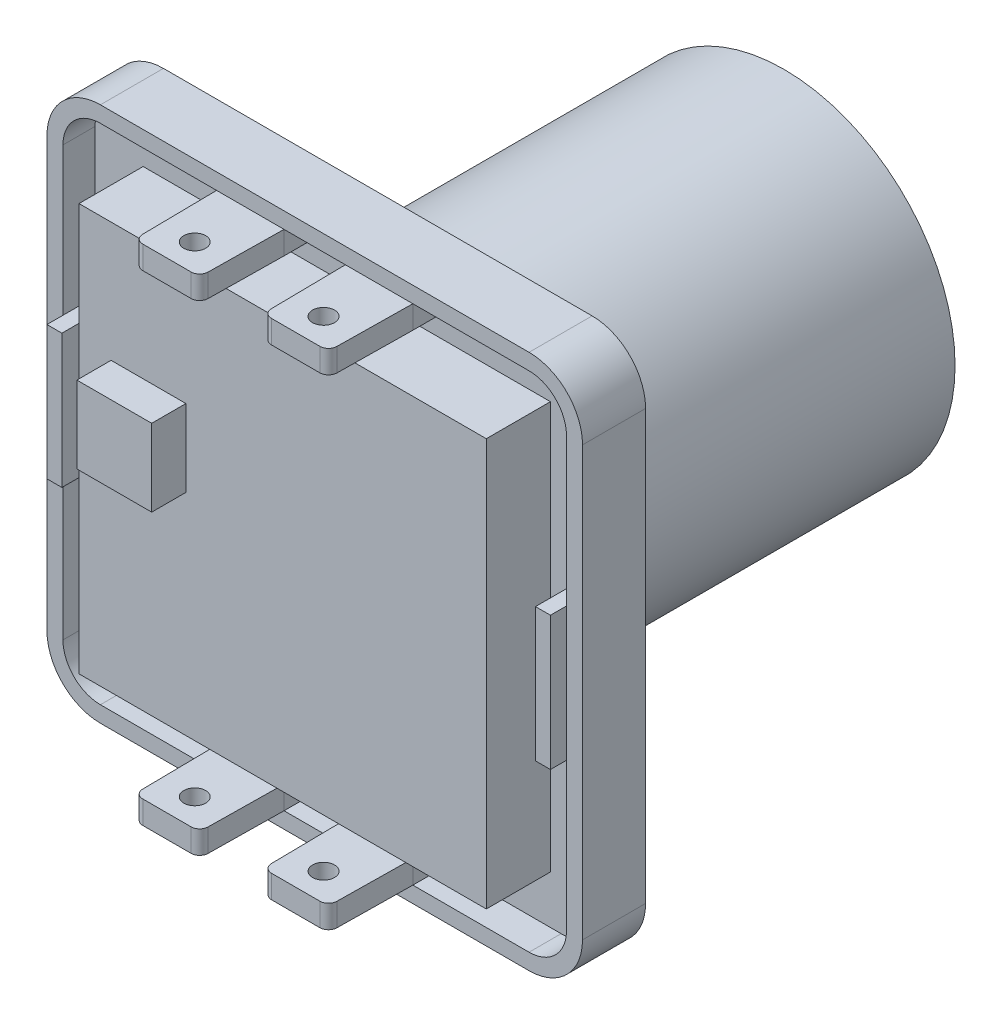
SolidWorks part; units mm, degrees
ref_plane "前视基准面" through (0, 0, 0) normal (0, 0, 1) x (1, 0, 0)
ref_plane "上视基准面" through (0, 0, 0) normal (0, 1, 0) x (1, 0, 0)
ref_plane "右视基准面" through (0, 0, 0) normal (1, 0, 0) x (0, 0, -1)
sketch "草图1" plane through (0, 0, 0) normal (0, 0, 1) x (1, 0, 0)
  line L1 (-25.05, 25.05) -> (25.05, 25.05)
  line L2 (-25.05, 25.05) -> (-25.05, -25.05)
  line L3 (-25.05, -25.05) -> (25.05, -25.05)
  line L4 (25.05, 25.05) -> (25.05, -25.05)
  line L5 (-25.05, 25.05) -> (25.05, -25.05) construction
  line L6 (-25.05, -25.05) -> (25.05, 25.05) construction
  point P0 (0, 0)
  dimension "D1" = 50.1
  dimension "D2" = 50.1
extrude "凸台-拉伸1" add sketch "草图1" against normal blind 5.9
sketch "草图2" plane through (0, 0, 0) normal (0, 0, 1) x (1, 0, 0)
  line L0 (25.05, -25.05) -> (25.05, 25.05) construction
  line L1 (22.15, 6.25) -> (23.55, 6.25)
  line L2 (22.15, 6.25) -> (22.15, -6.25)
  line L3 (22.15, -6.25) -> (23.55, -6.25)
  line L4 (23.55, 6.25) -> (23.55, -6.25)
  line L5 (22.15, 6.25) -> (23.55, -6.25) construction
  line L6 (22.15, -6.25) -> (23.55, 6.25) construction
  point P0 (22.85, 0)
  dimension "D1" = 12.5
  dimension "D2" = 1.5
  dimension "D3" = 1.4
extrude "凸台-拉伸2" add sketch "草图2" along normal blind 1.5
mirror "镜向1" about plane through (0, 0, 0) normal (1, 0, 0) of "凸台-拉伸2"
sketch "草图3" plane through (0, 0, 0) normal (0, 0, 1) x (1, 0, 0)
  line L0 (-2.87, 23.55) -> (-2.87, 21.4)
  line L1 (-9.18, 23.55) -> (9.18, 23.55)
  line L2 (-9.18, 23.55) -> (-9.18, 21.4)
  line L3 (-9.18, 21.4) -> (9.18, 21.4)
  line L4 (9.18, 23.55) -> (9.18, 21.4)
  line L5 (-9.18, 23.55) -> (9.18, 21.4) construction
  line L6 (-9.18, 21.4) -> (9.18, 23.55) construction
  line L7 (2.87, 23.55) -> (2.87, 21.4)
  line L8 (25.05, 25.05) -> (-25.05, 25.05) construction
  point P0 (0, 22.475)
  dimension "D1" = 1.5
  dimension "D2" = 18.36
  dimension "D3" = 2.15
  dimension "D4" = 5.74
  dimension "D5" = 2.87
extrude "凸台-拉伸3" add sketch "草图3" along normal blind 7.8 contours L2 L3 L0 L1 | L1 L7 L3 L4 region at (-6.025, 22.475, 0) region at (6.025, 22.475, 0)
sketch "草图5" plane through (0, 23.55, 0) normal (0, 1, 0) x (1, 0, 0)
  line L0 (-9.18, 0) -> (-9.075, -7.8)
  line L1 (-9.18, -7.8) -> (-2.87, -7.8) construction
  line L2 (-9.075, -7.8) -> (-9.18, -7.8)
  line L3 (-9.18, -7.8) -> (-9.18, 0)
  line L4 (-6.025, 0) -> (-6.025, -7.8) construction
  line L5 (-9.18, 0) -> (-2.87, 0) construction
  line L6 (-2.87, -7.8) -> (-2.87, 0)
  line L7 (-2.975, -7.8) -> (-2.87, -7.8)
  line L8 (-2.87, 0) -> (-2.975, -7.8)
  dimension "D1" = 6.1
extrude "切除-拉伸1" cut sketch "草图5" against normal blind 7.8
mirror "镜向2" about plane through (0, 0, 0) normal (1, 0, 0) of "切除-拉伸1"
sketch "草图6" plane through (0, 23.55, 0) normal (0, 1, 0) x (1, 0, 0)
  line L0 (-6.025, 0) -> (-6.025, -7.8) construction
  line L1 (-9.18, 0) -> (-2.87, 0) construction
  line L2 (-9.075, -7.8) -> (-2.975, -7.8) construction
  line L3 (0, 0) -> (0, -3.8203) construction
  circle A0 centre (-6.025, -5.2) radius 1
  circle A1 centre (6.025, -5.2) radius 1
  dimension "D1" = 2.6
  dimension "D2" = 2
extrude "切除-拉伸2" cut sketch "草图6" against normal blind 7.8
hole_wizard "M2.5 螺纹孔1" positions "草图7" profile "草图8" tap size "M2.5" standard "GB" end condition through all
sketch "草图7" plane through (0, 23.55, 0) normal (0, 1, 0) x (1, 0, 0)
  point P0 (-6.025, -5.2)
  point P3 (6.025, -5.2)
sketch "草图8" plane through (-6.025, 23.55, 5.2) normal (1, 0, 0) x (0, 0, 1)
  line L0 (0, 0) -> (0, 48.6)
  line L1 (0, 48.6) -> (1.025, 48.6)
  line L2 (1.025, 48.6) -> (1.025, 0)
  line L5 (1.025, 0) -> (0, 0)
  line L11 (0, -6.35) -> (0, 107.95) construction
  dimension "通孔螺纹孔钻头直径" = 2.05
  dimension "通孔螺纹孔钻头深度" = 48.6
cosmetic thread "孔螺蚊线1" parameters "D2"=2.5
cosmetic thread "孔螺蚊线2" parameters "D2"=2.5
fillet "圆角1" radius 0.8 4 edges at (9.075, 22.475, 7.8) (2.975, 22.475, 7.8) (-2.975, 22.475, 7.8) (-9.075, 22.475, 7.8)
mirror "镜向3" about plane through (0, 0, 0) normal (0, 1, 0) of "凸台-拉伸3", "切除-拉伸1", "镜向2", "M2.5 螺纹孔1", "切除-拉伸2", "圆角1"
sketch "草图9" plane through (0, 0, 0) normal (0, 0, 1) x (1, 0, 0)
  line L1 (-19.05, 19.05) -> (19.05, 19.05)
  line L2 (-19.05, 19.05) -> (-19.05, -19.05)
  line L3 (-19.05, -19.05) -> (19.05, -19.05)
  line L4 (19.05, 19.05) -> (19.05, -19.05)
  line L5 (-19.05, 19.05) -> (19.05, -19.05) construction
  line L6 (-19.05, -19.05) -> (19.05, 19.05) construction
  point P0 (0, 0)
  dimension "D1" = 38.1
extrude "凸台-拉伸4" add sketch "草图9" along normal blind 3
sketch "草图10" plane through (0, 0, 0) normal (0, 0, 1) x (1, 0, 0)
  line L0 (25.05, 25.05) -> (-25.05, 25.05) construction
  line L1 (-23.55, 23.55) -> (23.55, 23.55)
  line L2 (-23.55, 23.55) -> (-23.55, -23.55)
  line L3 (-23.55, -23.55) -> (23.55, -23.55)
  line L4 (23.55, 23.55) -> (23.55, -23.55)
  line L5 (-23.55, 23.55) -> (23.55, -23.55) construction
  line L6 (-23.55, -23.55) -> (23.55, 23.55) construction
  line L7 (25.05, -25.05) -> (25.05, 25.05) construction
  point P0 (0, 0)
  line M1 (2.87, -21.4) -> (9.18, -21.4)
  line M2 (9.18, -21.4) -> (9.18, -23.55)
  line M4 (2.87, -23.55) -> (2.87, -21.4)
  line M5 (-9.18, -23.55) -> (-9.18, -21.4)
  line M6 (-9.18, -21.4) -> (-2.87, -21.4)
  line M7 (-2.87, -21.4) -> (-2.87, -23.55)
  line M9 (9.18, 23.55) -> (9.18, 21.4)
  line M10 (9.18, 21.4) -> (2.87, 21.4)
  line M11 (2.87, 21.4) -> (2.87, 23.55)
  line M13 (-2.87, 21.4) -> (-9.18, 21.4)
  line M14 (-9.18, 21.4) -> (-9.18, 23.55)
  line M16 (-2.87, 23.55) -> (-2.87, 21.4)
  line M18 (-23.55, 6.25) -> (-22.15, 6.25)
  line M19 (-22.15, 6.25) -> (-22.15, -6.25)
  line M20 (-22.15, -6.25) -> (-23.55, -6.25)
  line M25 (22.15, 6.25) -> (23.55, 6.25)
  line M27 (23.55, -6.25) -> (22.15, -6.25)
  line M28 (22.15, -6.25) -> (22.15, 6.25)
  line M29 (-19.05, 19.05) -> (19.05, 19.05)
  line M30 (19.05, 19.05) -> (19.05, -19.05)
  line M31 (19.05, -19.05) -> (-19.05, -19.05)
  line M32 (-19.05, -19.05) -> (-19.05, 19.05)
  dimension "D1" = 1.5
  dimension "D2" = 1.5
extrude "切除-拉伸3" cut sketch "草图10" against normal blind 3 contours L4 L1 L2 L3 M9 M10 M11 M16 M13 M14 M18 M19 M20 M5 M6 M7 M4 M1 M2 M27 M28 M25 M32 M29 M30 M31 region at (-16.365, 22.8839, 0)
fillet "圆角2" radius 5 4 edges at (-25.05, 25.05, -2.95) (-25.05, -25.05, -2.95) (25.05, -25.05, -2.95) (25.05, 25.05, -2.95)
fillet "圆角3" radius 3.5 4 edges at (23.55, 23.55, -1.5) (-23.55, 23.55, -1.5) (-23.55, -23.55, -1.5) (23.55, -23.55, -1.5)
sketch "草图13" plane through (0, 0, -5.9) normal (0, 0, -1) x (-1, 0, 0)
  circle A0 centre (0, 0) radius 20
  dimension "D1" = 40
extrude "凸台-拉伸5" add sketch "草图13" along normal blind 1
chamfer "倒角1" distance 1 angle 45 1 edges at (-20, 0, -5.9)
sketch "草图14" plane through (0, 0, -6.9) normal (0, 0, -1) x (-1, 0, 0)
  circle A0 centre (0, 0) radius 18.25
  dimension "D1" = 36.5
extrude "凸台-拉伸6" add sketch "草图14" along normal blind 5
sketch "草图15" plane through (0, 0, -11.9) normal (0, 0, -1) x (-1, 0, 0)
  line L1 (20.05, -25.05) -> (-20.05, -25.05) construction
  line L2 (-18.208, -14.6725) -> (14.6725, 18.208)
  line L3 (-18.208, -14.6725) -> (-14.6725, -18.208)
  line L4 (14.6725, 18.208) -> (18.208, 14.6725)
  line L5 (-14.6725, -18.208) -> (18.208, 14.6725)
  line L6 (-18.208, -14.6725) -> (18.208, 14.6725) construction
  line L7 (14.6725, 18.208) -> (-14.6725, -18.208) construction
  dimension "D2" = 46.5
  dimension "D3" = 5
  dimension "D4" = 45
extrude "凸台-拉伸7" add sketch "草图15" against normal up to next (14.9 mm away)
pattern_circular "阵列(圆周)1" count 2 over 90 about axis through (0, 0, -11.9) along (0, 0, 1) of "凸台-拉伸7"
sketch "草图16" plane through (0, 0, 3) normal (0, 0, 1) x (1, 0, 0)
  line L0 (-19.05, 19.05) -> (19.05, 19.05) construction
  line L1 (-16.05, 7.85) -> (-9.05, 7.85)
  line L2 (-16.05, 7.85) -> (-16.05, 0.65)
  line L3 (-16.05, 0.65) -> (-9.05, 0.65)
  line L4 (-9.05, 7.85) -> (-9.05, 0.65)
  line L5 (-16.05, 7.85) -> (-9.05, 0.65) construction
  line L6 (-16.05, 0.65) -> (-9.05, 7.85) construction
  line L7 (-19.05, -19.05) -> (-19.05, 19.05) construction
  point P0 (-12.55, 4.25)
  dimension "D1" = 11.2
  dimension "D2" = 7.2
  dimension "D3" = 3
  dimension "D4" = 7
extrude "凸台-拉伸8" add sketch "草图16" along normal blind 3.2
sketch "草图17" plane through (0, 0, -11.9) normal (0, 0, -1) x (-1, 0, 0)
  circle A0 centre (0, 0) radius 16
  dimension "D1" = 32
extrude "凸台-拉伸9" add sketch "草图17" along normal blind 32
sketch "草图18" plane through (0, 0, -43.9) normal (0, 0, -1) x (-1, 0, 0)
  circle A0 centre (0, 0) radius 15
  circle A1 centre (0, 0) radius 16 construction
  dimension "D1" = 1
extrude "切除-拉伸4" cut sketch "草图18" against normal blind 5
dome "圆顶1" faces to dome 1 distance 5 reverse direction no elliptical dome no face at (-15, 0, -38.9) parameters "D1"=5
